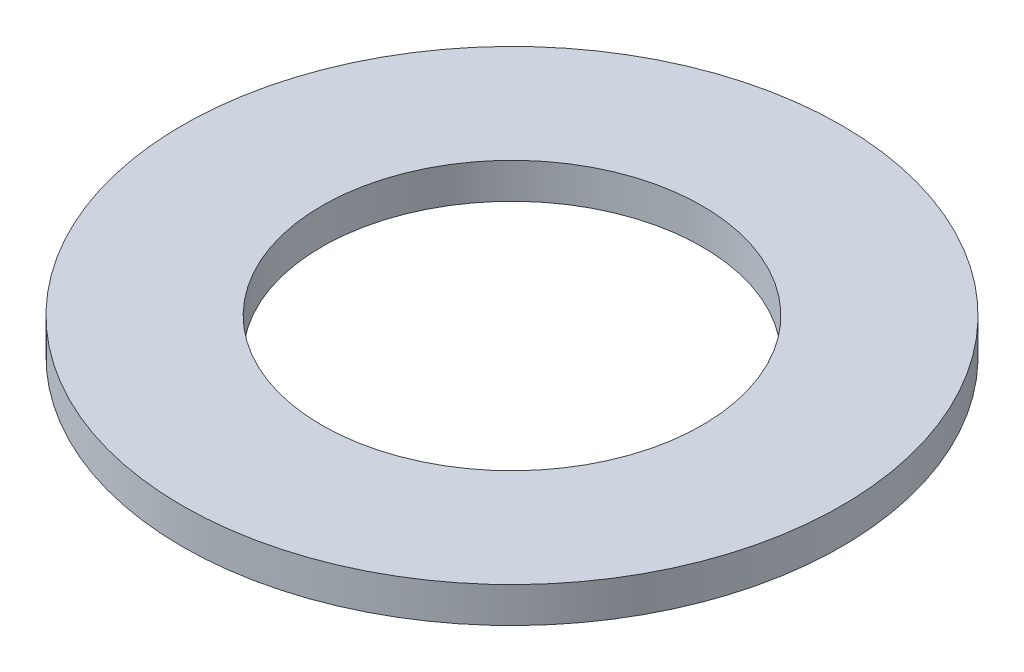
SolidWorks part; units mm, degrees
ref_plane "Front Plane" through (0, 0, 0) normal (0, 0, 1) x (1, 0, 0)
ref_plane "Top Plane" through (0, 0, 0) normal (0, 1, 0) x (1, 0, 0)
ref_plane "Right Plane" through (0, 0, 0) normal (1, 0, 0) x (0, 0, -1)
sketch "Sketch1" plane through (0, 0, 0) normal (0, 1, 0) x (1, 0, 0)
  circle A0 centre (0, 0) radius 65
  dimension "FLANGE_OD" = 130
extrude "Boss-Extrude1" add sketch "Sketch1" along normal blind 7
sketch "Sketch2" plane through (0, 0, 0) normal (0, 1, 0) x (1, 0, 0)
  circle A0 centre (0, 0) radius 37.5
  dimension "BORE_D" = 75
extrude "Cut-Extrude1" cut sketch "Sketch2" along normal through all
sketch "Sketch3" plane through (0, 7, 0) normal (0, 1, 0) x (1, 0, 0)
  circle A0 centre (0, 0) radius 21.5409 construction
  circle A1 centre (-21.5409, 0) radius 4.0987
  dimension "BOLT_D" = 8.1975
  dimension "BOLT_PCD" = 43.0818
extrude "Cut-Extrude2" cut sketch "Sketch3" against normal blind 4.9211 rebuild error yes
pattern_circular "CirPattern1" count 4 over 360 rebuild error yes
